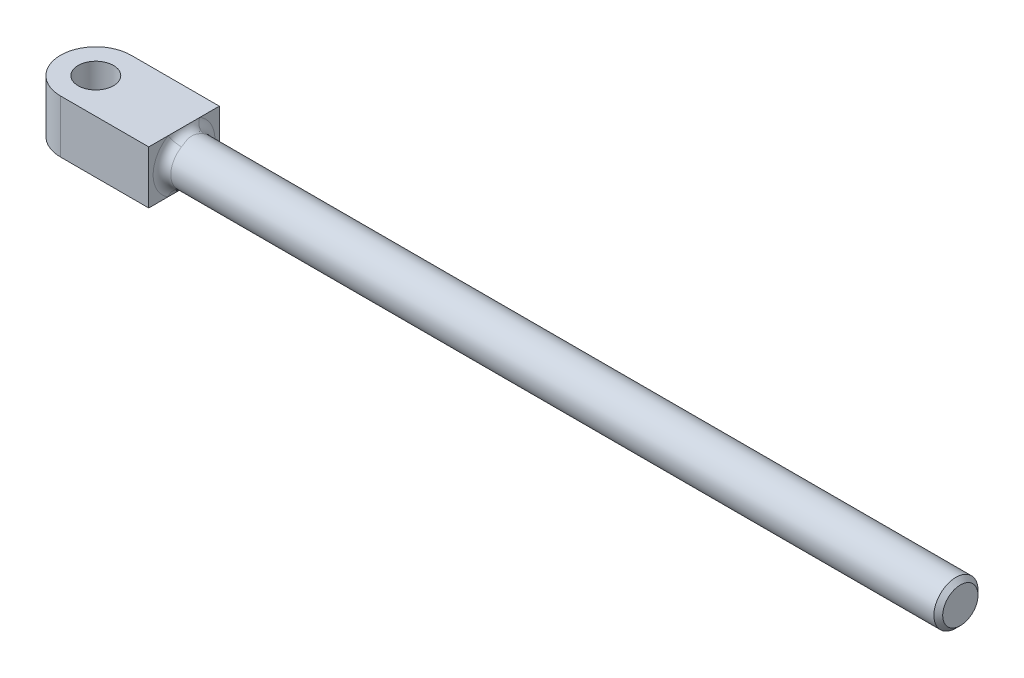
SolidWorks part; units mm, degrees
ref_plane "Front Plane" through (0, 0, 0) normal (0, 0, 1) x (1, 0, 0)
ref_plane "Top Plane" through (0, 0, 0) normal (0, 1, 0) x (1, 0, 0)
ref_plane "Right Plane" through (0, 0, 0) normal (1, 0, 0) x (0, 0, -1)
sketch "Sketch1" plane through (0, 0, 0) normal (1, 0, 0) x (0, 0, -1)
  circle A0 centre (0, 0) radius 2.5
  dimension "D1" = 5
extrude "Boss-Extrude1" add sketch "Sketch1" along normal mid plane 88
cosmetic thread "Cosmetic Thread1" parameters "D1"=14, "D2"=4.11
sketch "Sketch2" plane through (0, 0, 0) normal (0, 1, 0) x (1, 0, 0)
  line L0 (-44, 2.5) -> (-44, -2.5) construction
  line L1 (-44, 4) -> (-54, 4)
  line L2 (-44, 4) -> (-44, -4)
  line L3 (-44, -4) -> (-54, -4)
  arc A0 (-54, 4) -> (-54, -4) centre (-54, 0) ccw
  circle A1 centre (-54, 0) radius 2
  point P6 (-44, 0)
  dimension "D3" = 4
  dimension "D1" = 10
  dimension "D2" = 8
extrude "Boss-Extrude2" add sketch "Sketch2" along normal mid plane 6
fillet "Fillet1" radius 1 1 edges at (-44, 0, 2.5)
chamfer "Chamfer1" distance 0.5 angle 45 1 edges at (44, 0, -2.5)
